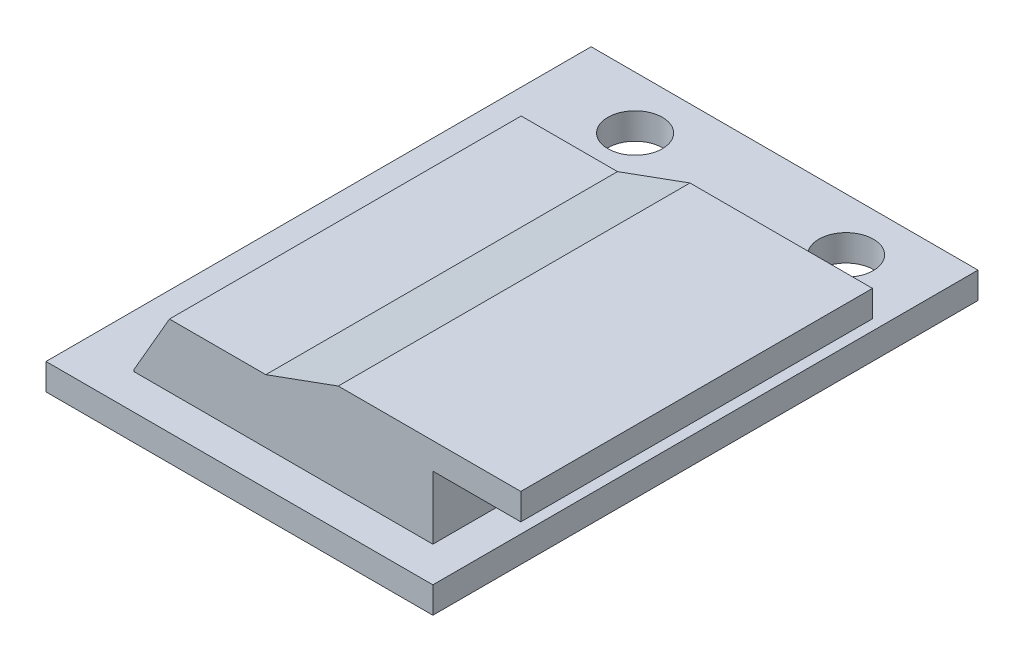
SolidWorks part; units mm, degrees
ref_plane "Ebene vorne" through (0, 0, 0) normal (0, 0, 1) x (1, 0, 0)
ref_plane "Ebene oben" through (0, 0, 0) normal (0, 1, 0) x (1, 0, 0)
ref_plane "Ebene rechts" through (0, 0, 0) normal (1, 0, 0) x (0, 0, -1)
sketch "Skizze2" plane through (0, 0, 0) normal (0, 1, 0) x (1, 0, 0)
  line L1 (8.5, -10) -> (-8.5, -10)
  line L2 (8.5, -10) -> (8.5, 10)
  line L3 (8.5, 10) -> (-8.5, 10)
  line L4 (-8.5, -10) -> (-8.5, 10)
  line L5 (8.5, -10) -> (-8.5, 10) construction
  line L6 (8.5, 10) -> (-8.5, -10) construction
  point P0 (0, 0)
  dimension "D1" = 20
  dimension "D2" = 17
extrude "Aufsatz-Linear austragen1" add sketch "Skizze2" along normal blind 3.6
sketch "Skizze3" plane through (0, 0, 0) normal (0, -1, 0) x (-1, 0, 0)
  line L1 (11.5, 19) -> (-10.5, 19)
  line L2 (11.5, 19) -> (11.5, -12)
  line L3 (11.5, -12) -> (-10.5, -12)
  line L4 (-10.5, 19) -> (-10.5, -12)
  line L5 (8.5, 10) -> (8.5, -10) construction
  line L7 (-8.5, 10) -> (8.5, 10) construction
  line L9 (8.5, -10) -> (-8.5, -10) construction
  dimension "D1" = 3
  dimension "D2" = 22
  dimension "D3" = 2
  dimension "D4" = 9
extrude "Aufsatz-Linear austragen2" add sketch "Skizze3" along normal blind 1.5
hole_wizard "Ø3.1 (3.1) Durchmesser Bohrung1" positions "Skizze8" profile "Skizze9" hole size "Ø3.1" standard "DIN" end condition through all
sketch "Skizze8" plane through (0, -1.5, 0) normal (0, -1, 0) x (-1, 0, 0)
  line L0 (-10.5, 19) -> (-10.5, -12) construction
  line L3 (-8.5, 10) -> (8.5, 10) construction
  point P0 (6, 16)
  point P2 (-6, 16)
  dimension "D1" = 4.5
  dimension "D2" = 12
  dimension "D3" = 6
  dimension "D4" = 6
sketch "Skizze9" plane through (-6, -1.5, -16) normal (1, 0, 0) x (0, 0, -1)
  line L0 (0, 0) -> (0, 5.1)
  line L1 (0, 5.1) -> (1.55, 5.1)
  line L2 (1.55, 5.1) -> (1.55, 0)
  line L5 (1.55, 0) -> (0, 0)
  line L11 (0, -6.35) -> (0, 107.95) construction
  dimension "Bohrerdurchmesser" = 3.1
  dimension "Bohrungstiefe" = 5.1
sketch "Skizze10" plane through (0, 3.6, 0) normal (0, 1, 0) x (1, 0, 0)
  line L0 (8.5, -10) -> (8.5, 10) construction
  line L1 (3.5, -10) -> (13.5, -10)
  line L2 (3.5, -10) -> (3.5, 10)
  line L3 (3.5, 10) -> (13.5, 10)
  line L4 (13.5, -10) -> (13.5, 10)
  line L5 (3.5, -10) -> (13.5, 10) construction
  line L6 (3.5, 10) -> (13.5, -10) construction
  line L7 (8.5, 10) -> (-8.5, 10) construction
  point P0 (8.5, 0)
  dimension "D1" = 5
extrude "Aufsatz-Linear austragen3" add sketch "Skizze10" along normal blind 1.5
chamfer "Fase4" distance 4.5 angle 20 1 edges at (3.5, 3.6, 0) first distance on face at (-2.5, 3.6, 0)
chamfer "Fase5" distance 3.5 angle 30 1 edges at (-8.5, 3.6, 0) first distance on face at (-8.5, 1.8, 0)
